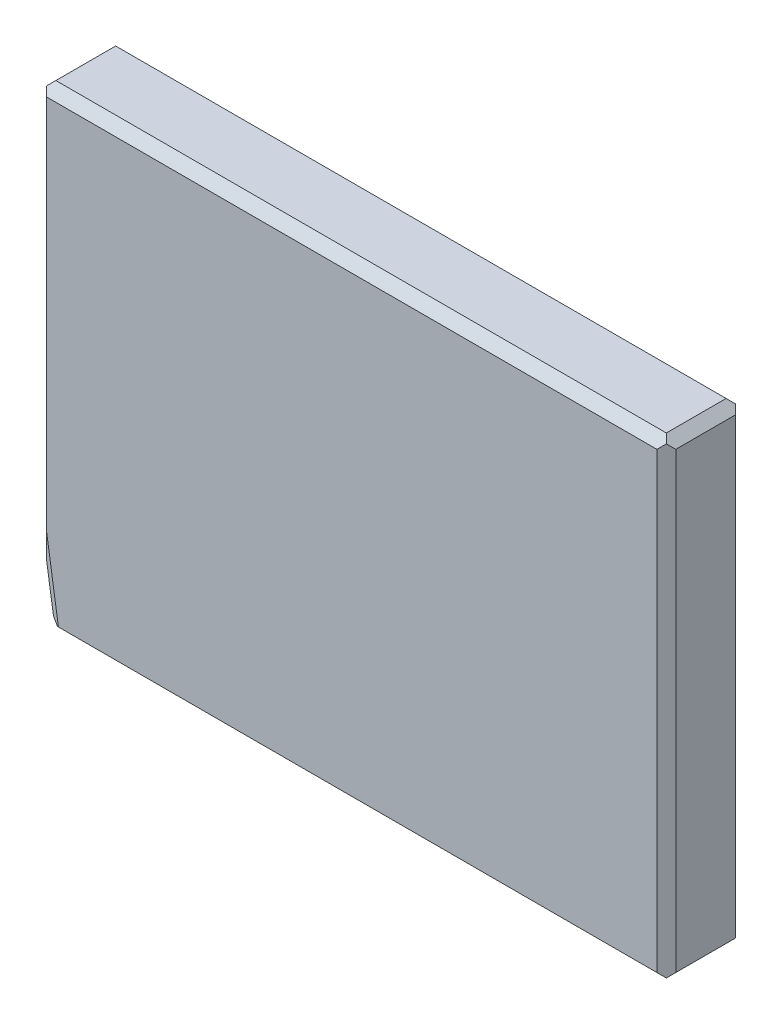
SolidWorks part; units mm, degrees
ref_plane "Front Plane" through (0, 0, 0) normal (0, 0, 1) x (1, 0, 0)
ref_plane "Top Plane" through (0, 0, 0) normal (0, 1, 0) x (1, 0, 0)
ref_plane "Right Plane" through (0, 0, 0) normal (1, 0, 0) x (0, 0, -1)
sketch "Sketch1" plane through (0, 0, 0) normal (0, 0, 1) x (1, 0, 0)
  line L1 (0, 0) -> (101.6, 0)
  line L2 (0, 0) -> (0, 76.2)
  line L3 (0, 76.2) -> (101.6, 76.2)
  line L4 (101.6, 0) -> (101.6, 76.2)
extrude "plate" add sketch "Sketch1" along normal blind 12.7
chamfer "Chamfer1" distance 1.524 angle 45 1 edges at (0, 0, 6.35)
chamfer "Chamfer3" distance 1.524 angle 45 1 edges at (0.762, 0.762, 0)
chamfer "Chamfer5" distance 1.524 angle 45 1 edges at (0.762, 0.762, 12.7)
chamfer "Chamfer7" distance 1.524 angle 45 1 edges at (0, 2.6016, 0.762) first distance on face at (1.3008, 1.3008, 0.762)
chamfer "Chamfer9" distance 1.524 angle 45 1 edges at (2.6016, 0, 0.762) first distance on face at (1.9607, 0.6409, 0.762)
chamfer "Chamfer10" distance 1.524 angle 45 1 edges at (0, 2.6016, 11.938) first distance on face at (1.3008, 1.3008, 11.938)
chamfer "Chamfer11" distance 1.524 angle 45 1 edges at (0.6599, 6.6252, 0) first distance on face at (0.5787, 3.116, 2.8524)
chamfer "Chamfer12" distance 1.524 angle 45 1 edges at (7.2062, 0.57, 0) first distance on face at (3.575, 0.6158, 2.3584)
chamfer "Chamfer14" distance 1.524 angle 45 1 edges at (0.9694, 0.9694, 2.5844) first distance on face at (3.0618, 0.4847, 3.3205)
chamfer "Chamfer18" distance 1.524 angle 45 1 edges at (0.6599, 6.6252, 12.7) first distance on face at (0.6338, 3.3713, 10.2798)
chamfer "Chamfer19" distance 1.524 angle 45 1 edges at (0, 16.3437, 0.7448) first distance on face at (1.2199, 8.3348, 0.757)
chamfer "Chamfer27" distance 1.524 angle 45 1 edges at (2.5175, 0, 11.8785) first distance on face at (1.9187, 0.1143, 11.5359)
chamfer "Chamfer29" distance 1.524 angle 45 1 edges at (101.6, 0, 6.35)
chamfer "Chamfer33" distance 1.524 angle 45 1 edges at (101.6, 76.2, 6.35)
chamfer "Chamfer37" distance 1.524 angle 45 1 edges at (0, 76.2, 6.35)
chamfer "Chamfer41" distance 1.524 angle 45 1 edges at (50.8, 76.2, 12.7)
chamfer "Chamfer43" distance 1.524 angle 45 1 edges at (101.6, 38.1, 12.7)
chamfer "Chamfer47" distance 1.524 angle 45 1 edges at (55.4835, 0, 12.7)
chamfer "Chamfer52" distance 1.524 angle 45 1 edges at (0, 49.2895, 12.7)
chamfer "Chamfer57" distance 1.524 angle 45 1 edges at (50.8, 76.2, 0)
chamfer "Chamfer59" distance 1.524 angle 45 1 edges at (101.6, 38.1, 0)
chamfer "Chamfer63" distance 1.524 angle 45 1 edges at (61.9895, 0, 0)
chamfer "Chamfer68" distance 1.524 angle 45 1 edges at (0, 74.4158, 0)
